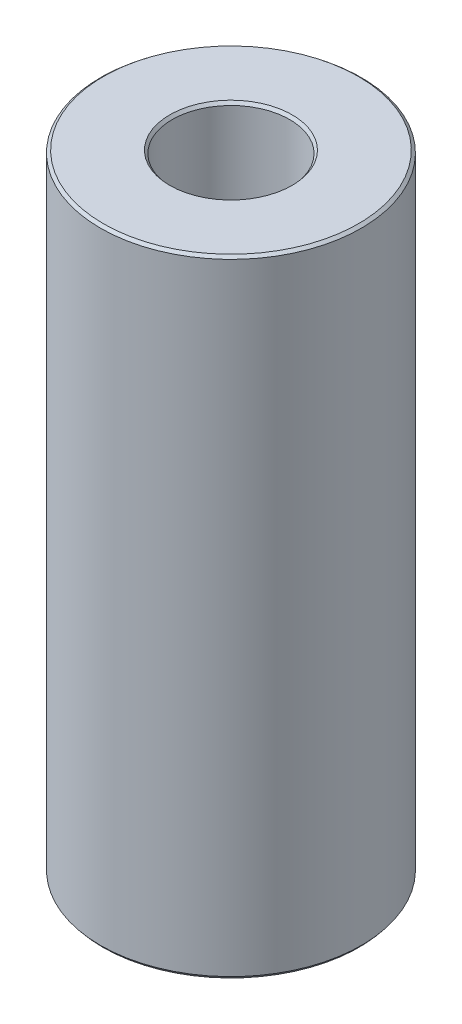
SolidWorks part; units mm, degrees
ref_plane "Front Plane" through (0, 0, 0) normal (0, 0, 1) x (1, 0, 0)
ref_plane "Top Plane" through (0, 0, 0) normal (0, 1, 0) x (1, 0, 0)
ref_plane "Right Plane" through (0, 0, 0) normal (1, 0, 0) x (0, 0, -1)
sketch "Sketch1" plane through (0, 0, 0) normal (0, 1, 0) x (1, 0, 0)
  circle A0 centre (0, 0) radius 35
  dimension "SLEEVE_OD" = 70
extrude "Boss-Extrude1" add sketch "Sketch1" along normal blind 168.0644
sketch "Sketch2" plane through (0, 0, 0) normal (0, 1, 0) x (1, 0, 0)
  circle A0 centre (0, 0) radius 15.773
  dimension "BORE_D" = 31.546
extrude "Cut-Extrude1" cut sketch "Sketch2" along normal through all
chamfer "Chamfer1" distance 0.644 angle 50.564 4 edges at (0, 168.0644, 15.773) (0, 0, 15.773) (0, 0, 35) (0, 168.0644, 35) first distance on face at (0, 168.0644, 15.773) first distance on face at (0, 0, 15.773) first distance on face at (0, 168.0644, 35)
